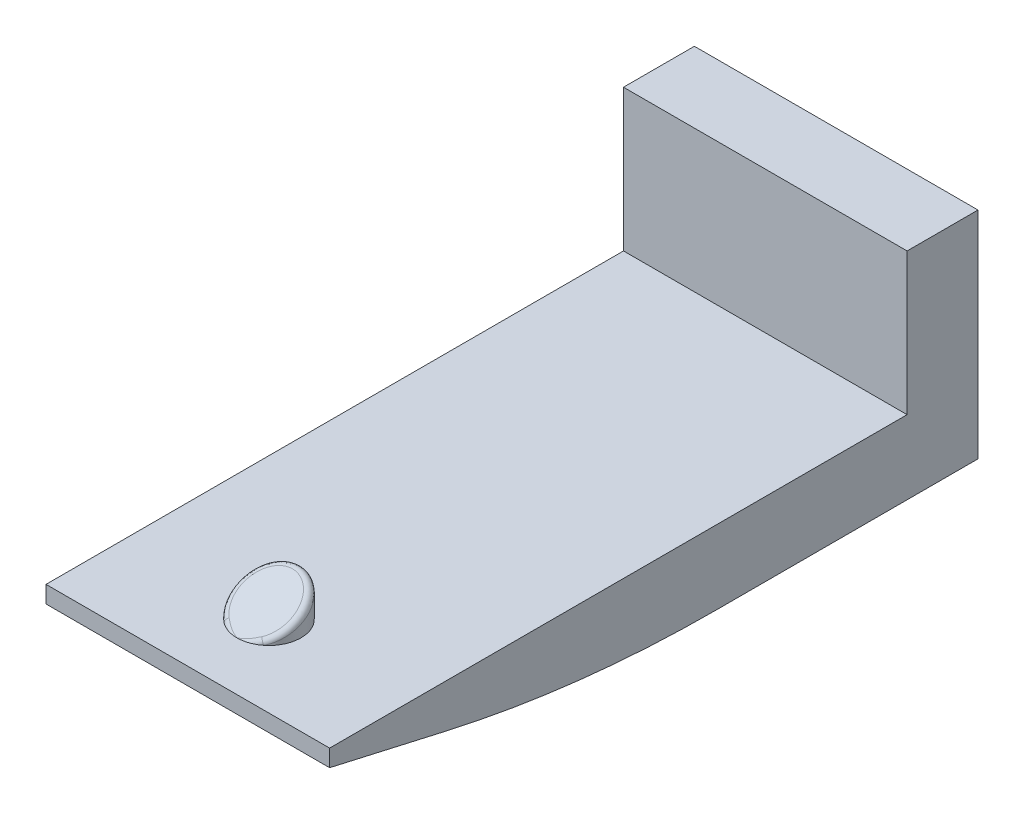
SolidWorks part; units mm, degrees
ref_plane "Front Plane" through (0, 0, 0) normal (0, 0, 1) x (1, 0, 0)
ref_plane "Top Plane" through (0, 0, 0) normal (0, 1, 0) x (1, 0, 0)
ref_plane "Right Plane" through (0, 0, 0) normal (1, 0, 0) x (0, 0, -1)
sketch "Sketch1" plane through (0, 0, 0) normal (1, 0, 0) x (0, 0, -1)
  line L0 (-32.385, 0) -> (0, 0)
  line L1 (0, 0) -> (0, 9.652)
  line L2 (0, 9.652) -> (-3.175, 9.652)
  line L3 (-3.175, 9.652) -> (-3.175, 3.302)
  line L4 (-3.175, 3.302) -> (-32.385, 3.302)
  line L5 (-32.385, 3.302) -> (-32.385, 0)
  line L6 (-29.0357, 3.302) -> (-29.0357, 2.54)
  line L7 (-32.385, 4.8006) -> (-32.385, 1.3716)
  line L8 (-32.385, 1.3716) -> (-23.9, 1.3716)
  line L9 (-23.9, 1.3716) -> (-23.9, 4.8006)
  line L10 (-23.9, 4.8006) -> (-32.385, 4.8006)
  line L11 (-25.4, 3.302) -> (-25.4, 4.8006) construction
  line L12 (-23.9, 4.8006) -> (-23.9, 3.302) construction
  line L13 (-32.385, 3.302) -> (-23.9, 1.3716)
  circle A1 centre (-3.175, 3.302) radius 1.016
  arc A2 (-11.6883, 0) -> (-23.9, 1.3716) centre (-11.6883, 55.0476) cw
  point P17 (3.5917, 0)
  dimension "D5" = 2.032
  dimension "D3" = 3.175
  dimension "D1" = 3.302
  dimension "D2" = 29.21
  dimension "D4" = 6.35
  dimension "D7" = 1.4986
  dimension "D8" = 3.429
  dimension "D10" = 1.5
  dimension "D6" = 0.762
  dimension "D9" = 22.225
extrude "Boss-Extrude1" add sketch "Sketch1" along normal blind 12.7 contours L5 L13 L9 L4 | L1 L2 L3 A1 L4 L9 | L4 A1 L3 region at (0, 2.7545, 9.3516) region at (0, 2.5866, 26.0964) region at (0, 3.1583, 3.0313)
sketch "Sketch2" plane through (0, 3.302, 0) normal (0, 1, 0) x (1, 0, 0)
  line L0 (12.7, -3.175) -> (0, -3.175) construction
  line L4 (12.7, -32.385) -> (0, -32.385) construction
  circle A0 centre (6.35, -25.4) radius 1.4351
  point P5 (6.35, -32.385)
  dimension "D1" = 2.8702
  dimension "D2" = 22.225
extrude "Boss-Extrude2" add sketch "Sketch2" along normal blind 3.302
sketch "Sketch3" plane through (12.7, 0, 0) normal (1, 0, 0) x (0, 0, -1)
  line L0 (-26.8351, 3.302) -> (-23.9649, 4.953)
  line L1 (-23.9649, 3.302) -> (-23.9649, 6.604) construction
  line L2 (-23.9649, 4.953) -> (-23.9649, 6.604)
  line L3 (-23.9649, 6.604) -> (-26.8351, 6.604)
  line L4 (-26.8351, 6.604) -> (-26.8351, 3.302)
extrude "Cut-Extrude1" cut sketch "Sketch3" against normal through all contours L4 L0 L2 L3
fillet "Fillet1" radius 0.254 1 edges at (6.35, 3.302, 26.8351)
fillet "Fillet2" [suppressed] radius 1.27
equation "\"WallThickness\"=0.125"
equation "\"D9@Sketch1\"=\"WallThickness\"+.75"
equation "\"D2@Sketch2\"=\"WallThickness\"+.75"
